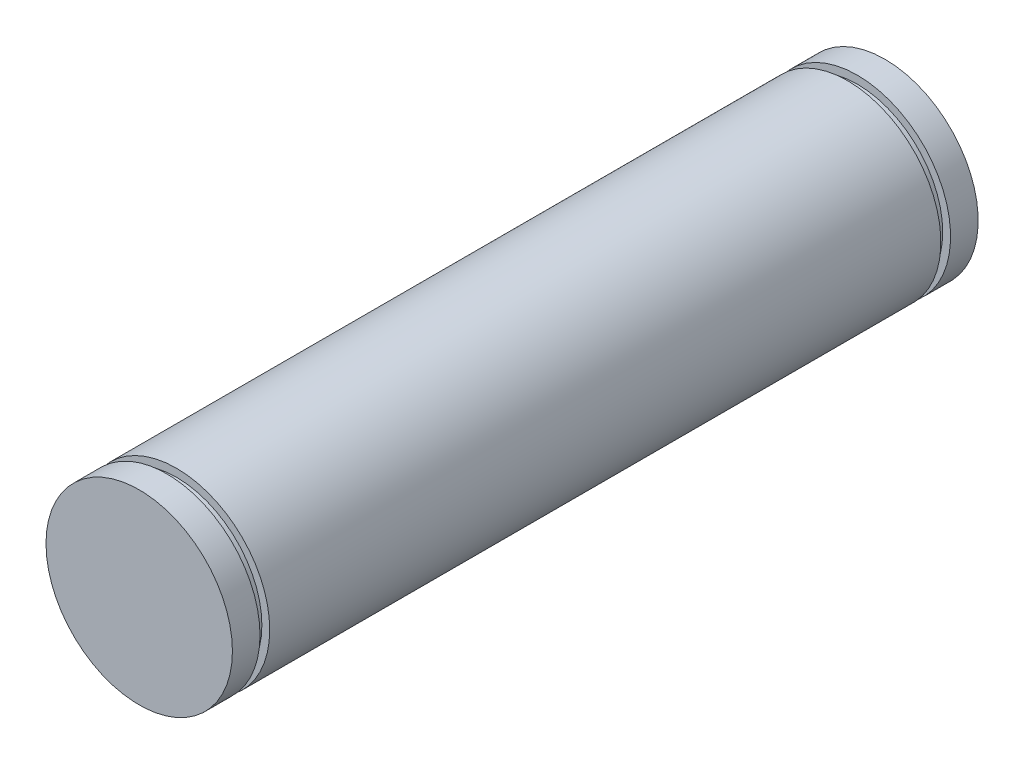
SolidWorks part; units mm, degrees
material "AISI 1045 钢，冷拔"
ref_plane "前视基准面" through (0, 0, 0) normal (0, 0, 1) x (1, 0, 0)
ref_plane "上视基准面" through (0, 0, 0) normal (0, 1, 0) x (1, 0, 0)
ref_plane "右视基准面" through (0, 0, 0) normal (1, 0, 0) x (0, 0, -1)
sketch "草图1" plane through (0, 0, 5503) normal (0, 0, 1) x (1, 0, 0)
  circle A0 centre (1309.3248, 736.6355) radius 12.5
  dimension "D1" = 25
extrude "凸台-拉伸1" add sketch "草图1" along normal blind 5
extrude "凸台-拉伸2" add sketch "草图1<2>" against normal offset from surface (95 mm away) 5 offset beyond the face yes
sketch "草图1<2>" plane through (0, 0, 5503) normal (0, 0, 1) x (1, 0, 0) same geometry as "草图1"
ref_plane "基准面1" through (0, 0, 5503) normal (0, 0, 1) x (1, 0, 0)
sketch "草图2" plane through (0, 0, 5503) normal (0, 0, 1) x (1, 0, 0)
  circle A0 centre (1309.3248, 736.6355) radius 11.45
  dimension "D1" = 22.9
extrude "切除-拉伸1" cut sketch "草图2" along normal blind 1.3 flip side to cut
ref_plane "基准面2" through (0, 0, 5413) normal (0, 0, -1) x (-1, 0, 0)
sketch "草图3" plane through (0, 0, 5413) normal (0, 0, -1) x (-1, 0, 0)
  circle A0 centre (-1309.3248, 736.6355) radius 11.45
  dimension "D1" = 22.9
extrude "切除-拉伸2" cut sketch "草图3" along normal blind 1.3 flip side to cut
